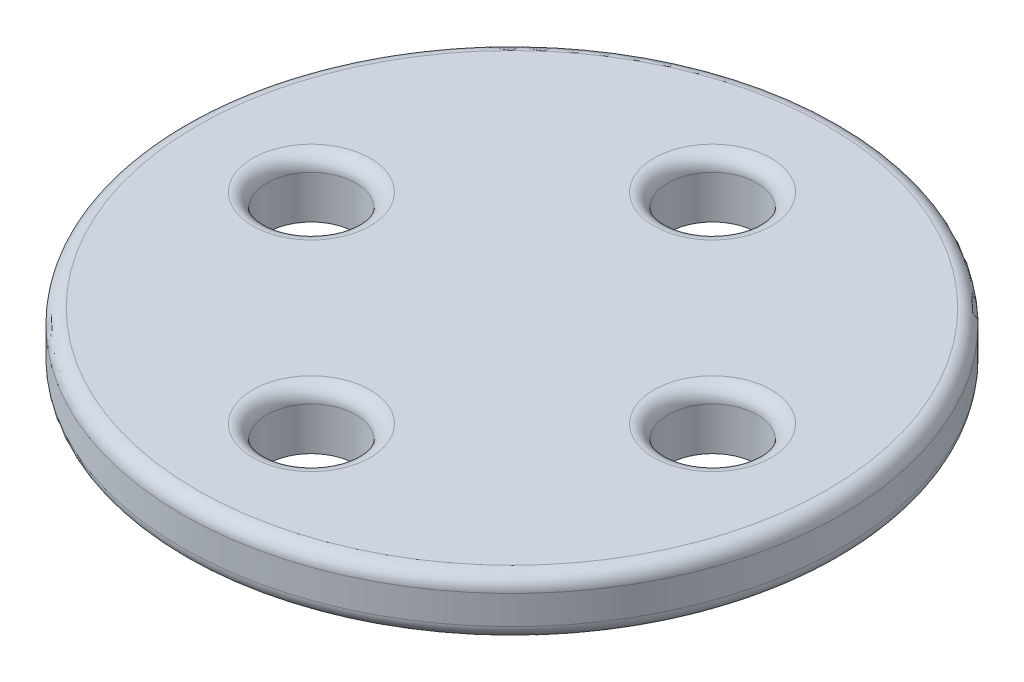
SolidWorks part; units mm, degrees
other "graphite_1"
other "blue_2"
other "white_6"
other "white_7"
other "white_10"
other "white_3"
other "white_2"
ref_plane "Front Plane" through (0, 0, 0) normal (0, 0, 1) x (1, 0, 0)
ref_plane "Top Plane" through (0, 0, 0) normal (0, 1, 0) x (1, 0, 0)
ref_plane "Right Plane" through (0, 0, 0) normal (1, 0, 0) x (0, 0, -1)
sketch "Sketch1" plane through (0, 0, 0) normal (0, 1, 0) x (1, 0, 0)
  line L0 (0, 7) -> (0, 0) construction
  circle A0 centre (0, 0) radius 11.5
  circle A1 centre (0, 7) radius 1.55
  circle A2 centre (7, 0) radius 1.55
  circle A3 centre (0, -7) radius 1.55
  circle A4 centre (-7, 0) radius 1.55
  point P14 (0, 0)
  dimension "D1" = 23
  dimension "D2" = 3.1
  dimension "D3" = 7
  dimension "D4" = 4
extrude "Boss-Extrude1" add sketch "Sketch1" along normal blind 2
fillet "Fillet1" radius 0.5 6 edges at (-7, 2, 1.55) (7, 2, 1.55) (0, 2, 11.5) (0, 2, -5.45) (0, 2, 8.55) (0, 0, 11.5)
sketch "Sketch2" [suppressed] plane through (0, 2, 0) normal (0, 1, 0) x (1, 0, 0)
  line L0 (-2.4749, -2.4749) -> (2.4749, 2.4749) construction
  line L3 (-4.2426, -0.7071) -> (0.7071, 4.2426) construction
  line L4 (-0.7071, -4.2426) -> (4.2426, 0.7071) construction
  line L5 (0, 0) -> (23.072, 0) construction
  line L6 (-6.364, -2.1213) -> (-2.1213, -6.364) construction
  line L7 (-2.1213, -6.364) -> (6.364, 2.1213) construction
  line L8 (6.364, 2.1213) -> (2.1213, 6.364) construction
  line L9 (2.1213, 6.364) -> (-6.364, -2.1213) construction
  line L10 (-6.364, -2.1213) -> (6.364, 2.1213) construction
  line L11 (2.1213, 6.364) -> (6.364, 2.1213)
  line L12 (6.364, 2.1213) -> (4.9497, 0.7071)
  line L13 (2.1213, 6.364) -> (0.7071, 4.9497)
  line L14 (-6.364, -2.1213) -> (-4.9497, -0.7071)
  line L15 (-6.364, -2.1213) -> (-2.1213, -6.364)
  line L16 (-2.1213, -6.364) -> (-0.7071, -4.9497)
  circle A0 centre (-7, 0) radius 2.75 construction
  circle A1 centre (0, 7) radius 2.75 construction
  circle A2 centre (7, 0) radius 2.75 construction
  circle A3 centre (0, -7) radius 2.75 construction
  arc A6 (-4.2426, -0.7071) -> (-0.7071, -4.2426) centre (-2.4749, -2.4749) ccw construction
  arc A7 (4.2426, 0.7071) -> (0.7071, 4.2426) centre (2.4749, 2.4749) ccw construction
  circle A8 centre (0, 0) radius 5 construction
  arc A10 (-0.7071, -4.9497) -> (4.9497, 0.7071) centre (0, 0) ccw
  arc A12 (0.7071, 4.9497) -> (-4.9497, -0.7071) centre (0, 0) ccw
  point P13 (0, 0)
  dimension "D1" = 5.5
  dimension "D2" = 12
  dimension "D3" = 5
  dimension "D7" = 10
  dimension "D4" = 45
  dimension "D5" = 6
  dimension "D6" = 12
extrude "Cable hole" [suppressed] cut sketch "Sketch2" against normal through all
fillet "Fillet2" [suppressed] radius 1
sketch "GL_F_side_blue" plane through (0, 0, 0) normal (0, 1, 0) x (1, 0, 0)
  line L0 (4.1012, -5.7912) -> (3.5426, -5.2326)
  line L1 (3.5426, -5.2326) -> (4.0376, -4.7376)
  line L2 (4.0376, -4.7376) -> (3.7477, -4.4477)
  line L3 (3.7477, -4.4477) -> (3.2527, -4.9427)
  line L4 (3.2527, -4.9427) -> (2.6941, -4.3841)
  line L5 (2.6941, -4.3841) -> (3.1891, -3.8891)
  line L6 (3.1891, -3.8891) -> (1.2092, -1.9092)
  line L7 (1.2092, -1.9092) -> (1.3233, -1.795)
  line L8 (1.3233, -1.795) -> (-1.795, -1.795)
  line L9 (-1.795, -1.795) -> (-1.795, 1.3233)
  line L10 (-1.795, 1.3233) -> (-1.9092, 1.2092)
  line L11 (-1.9092, 1.2092) -> (-4.852, 4.1519)
  line L12 (-4.852, 4.1519) -> (-4.7161, 4.1794)
  line L13 (-4.7161, 4.1794) -> (-4.5701, 4.2398)
  line L14 (-4.5701, 4.2398) -> (-4.3805, 4.3805)
  line L15 (-4.3805, 4.3805) -> (-4.2398, 4.5701)
  line L16 (-4.2398, 4.5701) -> (-4.1794, 4.7161)
  line L17 (-4.1794, 4.7161) -> (-4.1519, 4.852)
  line L18 (-4.1519, 4.852) -> (-1.2092, 1.9092)
  line L19 (-1.2092, 1.9092) -> (-1.3233, 1.795)
  line L20 (-1.3233, 1.795) -> (1.3233, 1.795)
  line L21 (1.3233, 1.795) -> (1.2092, 1.9092)
  line L22 (1.2092, 1.9092) -> (5.6637, 6.3638)
  line L23 (5.6637, 6.3638) -> (5.6872, 6.2571)
  line L24 (5.6872, 6.2571) -> (5.7514, 6.1022)
  line L25 (5.7514, 6.1022) -> (5.9008, 5.9008)
  line L26 (5.9008, 5.9008) -> (6.1022, 5.7514)
  line L27 (6.1022, 5.7514) -> (6.2571, 5.6872)
  line L28 (6.2571, 5.6872) -> (6.3638, 5.6637)
  line L29 (6.3638, 5.6637) -> (1.9092, 1.2092)
  line L30 (1.9092, 1.2092) -> (1.795, 1.3233)
  line L31 (1.795, 1.3233) -> (1.795, -1.3233)
  line L32 (1.795, -1.3233) -> (1.9092, -1.2092)
  line L33 (1.9092, -1.2092) -> (3.8891, -3.1891)
  line L34 (3.8891, -3.1891) -> (4.3841, -2.6941)
  line L35 (4.3841, -2.6941) -> (4.9427, -3.2527)
  line L36 (4.9427, -3.2527) -> (4.4477, -3.7477)
  line L37 (4.4477, -3.7477) -> (4.7376, -4.0376)
  line L38 (4.7376, -4.0376) -> (5.2326, -3.5426)
  line L39 (5.2326, -3.5426) -> (5.7912, -4.1012)
  line L40 (5.7912, -4.1012) -> (5.2962, -4.5962)
  line L41 (5.2962, -4.5962) -> (6.9933, -6.2933)
  line L42 (6.9933, -6.2933) -> (6.2933, -6.9933)
  line L43 (6.2933, -6.9933) -> (4.5962, -5.2962)
  line L44 (4.5962, -5.2962) -> (4.1012, -5.7912)
  line L45 (-0.2962, 0.7941) -> (-0.2962, 0.9029)
  line L46 (-0.2962, 0.9029) -> (-0.3174, 1.0096)
  line L47 (-0.3174, 1.0096) -> (-0.359, 1.1102)
  line L48 (-0.359, 1.1102) -> (-0.4195, 1.2006)
  line L49 (-0.4195, 1.2006) -> (-0.4964, 1.2776)
  line L50 (-0.4964, 1.2776) -> (-0.5869, 1.338)
  line L51 (-0.5869, 1.338) -> (-0.6874, 1.3797)
  line L52 (-0.6874, 1.3797) -> (-0.7941, 1.4009)
  line L53 (-0.7941, 1.4009) -> (-0.9029, 1.4009)
  line L54 (-0.9029, 1.4009) -> (-1.0096, 1.3797)
  line L55 (-1.0096, 1.3797) -> (-1.1102, 1.338)
  line L56 (-1.1102, 1.338) -> (-1.2006, 1.2776)
  line L57 (-1.2006, 1.2776) -> (-1.2776, 1.2006)
  line L58 (-1.2776, 1.2006) -> (-1.338, 1.1102)
  line L59 (-1.338, 1.1102) -> (-1.3797, 1.0096)
  line L60 (-1.3797, 1.0096) -> (-1.4009, 0.9029)
  line L61 (-1.4009, 0.9029) -> (-1.4009, 0.7941)
  line L62 (-1.4009, 0.7941) -> (-1.3797, 0.6874)
  line L63 (-1.3797, 0.6874) -> (-1.338, 0.5869)
  line L64 (-1.338, 0.5869) -> (-1.2776, 0.4964)
  line L65 (-1.2776, 0.4964) -> (-1.2006, 0.4195)
  line L66 (-1.2006, 0.4195) -> (-1.1102, 0.359)
  line L67 (-1.1102, 0.359) -> (-1.0096, 0.3174)
  line L68 (-1.0096, 0.3174) -> (-0.9029, 0.2962)
  line L69 (-0.9029, 0.2962) -> (-0.7941, 0.2962)
  line L70 (-0.7941, 0.2962) -> (-0.6874, 0.3174)
  line L71 (-0.6874, 0.3174) -> (-0.5869, 0.359)
  line L72 (-0.5869, 0.359) -> (-0.4964, 0.4195)
  line L73 (-0.4964, 0.4195) -> (-0.4195, 0.4964)
  line L74 (-0.4195, 0.4964) -> (-0.359, 0.5869)
  line L75 (-0.359, 0.5869) -> (-0.3174, 0.6874)
  line L76 (-0.3174, 0.6874) -> (-0.2962, 0.7941)
extrude "GL_F_side_blue_raised" add sketch "GL_F_side_blue" along normal blind 0.6 from offset 0.6 separate body offset against normal yes
sketch "GL_F_side_white" plane through (0, 0, 0) normal (0, 1, 0) x (1, 0, 0)
  line L0 (-5.628, -6.3839) -> (-5.6958, -6.4665)
  line L1 (-5.6958, -6.4665) -> (-5.7783, -6.5342)
  line L2 (-5.7783, -6.5342) -> (-5.8726, -6.5846)
  line L3 (-5.8726, -6.5846) -> (-5.9748, -6.6156)
  line L4 (-5.9748, -6.6156) -> (-6.0811, -6.6261)
  line L5 (-6.0811, -6.6261) -> (-6.1874, -6.6156)
  line L6 (-6.1874, -6.6156) -> (-6.2897, -6.5846)
  line L7 (-6.2897, -6.5846) -> (-6.3839, -6.5342)
  line L8 (-6.3839, -6.5342) -> (-6.4665, -6.4665)
  line L9 (-6.4665, -6.4665) -> (-6.5342, -6.3839)
  line L10 (-6.5342, -6.3839) -> (-6.5846, -6.2897)
  line L11 (-6.5846, -6.2897) -> (-6.6156, -6.1874)
  line L12 (-6.6156, -6.1874) -> (-6.6261, -6.0811)
  line L13 (-6.6261, -6.0811) -> (-6.6156, -5.9748)
  line L14 (-6.6156, -5.9748) -> (-6.5846, -5.8726)
  line L15 (-6.5846, -5.8726) -> (-6.5342, -5.7783)
  line L16 (-6.5342, -5.7783) -> (-6.4665, -5.6958)
  line L17 (-6.4665, -5.6958) -> (-6.3839, -5.628)
  line L18 (-6.3839, -5.628) -> (-6.2897, -5.5776)
  line L19 (-6.2897, -5.5776) -> (-6.1874, -5.5466)
  line L20 (-6.1874, -5.5466) -> (-6.0811, -5.5361)
  line L21 (-6.0811, -5.5361) -> (-5.9748, -5.5466)
  line L22 (-5.9748, -5.5466) -> (-5.8726, -5.5776)
  line L23 (-5.8726, -5.5776) -> (-5.7783, -5.628)
  line L24 (-5.7783, -5.628) -> (-5.6958, -5.6958)
  line L25 (-5.6958, -5.6958) -> (-5.628, -5.7783)
  line L26 (-5.628, -5.7783) -> (-5.5776, -5.8726)
  line L27 (-5.5776, -5.8726) -> (-5.5466, -5.9748)
  line L28 (-5.5466, -5.9748) -> (-5.5361, -6.0811)
  line L29 (-5.5361, -6.0811) -> (-5.5466, -6.1874)
  line L30 (-5.5466, -6.1874) -> (-5.5776, -6.2897)
  line L31 (-5.5776, -6.2897) -> (-5.628, -6.3839)
  line L32 (-3.7895, -4.5454) -> (-3.8573, -4.628)
  line L33 (-3.8573, -4.628) -> (-3.9399, -4.6958)
  line L34 (-3.9399, -4.6958) -> (-4.0341, -4.7461)
  line L35 (-4.0341, -4.7461) -> (-4.1363, -4.7771)
  line L36 (-4.1363, -4.7771) -> (-4.2426, -4.7876)
  line L37 (-4.2426, -4.7876) -> (-4.349, -4.7771)
  line L38 (-4.349, -4.7771) -> (-4.4512, -4.7461)
  line L39 (-4.4512, -4.7461) -> (-4.5454, -4.6958)
  line L40 (-4.5454, -4.6958) -> (-4.628, -4.628)
  line L41 (-4.628, -4.628) -> (-4.6958, -4.5454)
  line L42 (-4.6958, -4.5454) -> (-4.7461, -4.4512)
  line L43 (-4.7461, -4.4512) -> (-4.7771, -4.349)
  line L44 (-4.7771, -4.349) -> (-4.7876, -4.2426)
  line L45 (-4.7876, -4.2426) -> (-4.7771, -4.1363)
  line L46 (-4.7771, -4.1363) -> (-4.7461, -4.0341)
  line L47 (-4.7461, -4.0341) -> (-4.6958, -3.9399)
  line L48 (-4.6958, -3.9399) -> (-4.628, -3.8573)
  line L49 (-4.628, -3.8573) -> (-4.5454, -3.7895)
  line L50 (-4.5454, -3.7895) -> (-4.4512, -3.7391)
  line L51 (-4.4512, -3.7391) -> (-4.349, -3.7081)
  line L52 (-4.349, -3.7081) -> (-4.2426, -3.6977)
  line L53 (-4.2426, -3.6977) -> (-4.1363, -3.7081)
  line L54 (-4.1363, -3.7081) -> (-4.0341, -3.7391)
  line L55 (-4.0341, -3.7391) -> (-3.9399, -3.7895)
  line L56 (-3.9399, -3.7895) -> (-3.8573, -3.8573)
  line L57 (-3.8573, -3.8573) -> (-3.7895, -3.9399)
  line L58 (-3.7895, -3.9399) -> (-3.7391, -4.0341)
  line L59 (-3.7391, -4.0341) -> (-3.7081, -4.1363)
  line L60 (-3.7081, -4.1363) -> (-3.6977, -4.2426)
  line L61 (-3.6977, -4.2426) -> (-3.7081, -4.349)
  line L62 (-3.7081, -4.349) -> (-3.7391, -4.4512)
  line L63 (-3.7391, -4.4512) -> (-3.7895, -4.5454)
  line L64 (-0.3954, 0.5458) -> (-0.4632, 0.4632)
  line L65 (-0.4632, 0.4632) -> (-0.5458, 0.3954)
  line L66 (-0.5458, 0.3954) -> (-0.64, 0.345)
  line L67 (-0.64, 0.345) -> (-0.7422, 0.314)
  line L68 (-0.7422, 0.314) -> (-0.8485, 0.3036)
  line L69 (-0.8485, 0.3036) -> (-0.9548, 0.314)
  line L70 (-0.9548, 0.314) -> (-1.0571, 0.345)
  line L71 (-1.0571, 0.345) -> (-1.1513, 0.3954)
  line L72 (-1.1513, 0.3954) -> (-1.2339, 0.4632)
  line L73 (-1.2339, 0.4632) -> (-1.3017, 0.5458)
  line L74 (-1.3017, 0.5458) -> (-1.352, 0.64)
  line L75 (-1.352, 0.64) -> (-1.383, 0.7422)
  line L76 (-1.383, 0.7422) -> (-1.3935, 0.8485)
  line L77 (-1.3935, 0.8485) -> (-1.383, 0.9548)
  line L78 (-1.383, 0.9548) -> (-1.352, 1.0571)
  line L79 (-1.352, 1.0571) -> (-1.3017, 1.1513)
  line L80 (-1.3017, 1.1513) -> (-1.2339, 1.2339)
  line L81 (-1.2339, 1.2339) -> (-1.1513, 1.3017)
  line L82 (-1.1513, 1.3017) -> (-1.0571, 1.352)
  line L83 (-1.0571, 1.352) -> (-0.9548, 1.383)
  line L84 (-0.9548, 1.383) -> (-0.8485, 1.3935)
  line L85 (-0.8485, 1.3935) -> (-0.7422, 1.383)
  line L86 (-0.7422, 1.383) -> (-0.64, 1.352)
  line L87 (-0.64, 1.352) -> (-0.5458, 1.3017)
  line L88 (-0.5458, 1.3017) -> (-0.4632, 1.2339)
  line L89 (-0.4632, 1.2339) -> (-0.3954, 1.1513)
  line L90 (-0.3954, 1.1513) -> (-0.345, 1.0571)
  line L91 (-0.345, 1.0571) -> (-0.314, 0.9548)
  line L92 (-0.314, 0.9548) -> (-0.3036, 0.8485)
  line L93 (-0.3036, 0.8485) -> (-0.314, 0.7422)
  line L94 (-0.314, 0.7422) -> (-0.345, 0.64)
  line L95 (-0.345, 0.64) -> (-0.3954, 0.5458)
  line L96 (-4.3876, 4.3876) -> (-4.5081, 4.2887)
  line L97 (-4.5081, 4.2887) -> (-4.6455, 4.2153)
  line L98 (-4.6455, 4.2153) -> (-4.7947, 4.17)
  line L99 (-4.7947, 4.17) -> (-4.9497, 4.1548)
  line L100 (-4.9497, 4.1548) -> (-5.1048, 4.17)
  line L101 (-5.1048, 4.17) -> (-5.254, 4.2153)
  line L102 (-5.254, 4.2153) -> (-5.3914, 4.2887)
  line L103 (-5.3914, 4.2887) -> (-5.5119, 4.3876)
  line L104 (-5.5119, 4.3876) -> (-5.6107, 4.5081)
  line L105 (-5.6107, 4.5081) -> (-5.6842, 4.6455)
  line L106 (-5.6842, 4.6455) -> (-5.7294, 4.7947)
  line L107 (-5.7294, 4.7947) -> (-5.7447, 4.9497)
  line L108 (-5.7447, 4.9497) -> (-5.7294, 5.1048)
  line L109 (-5.7294, 5.1048) -> (-5.6842, 5.254)
  line L110 (-5.6842, 5.254) -> (-5.6107, 5.3914)
  line L111 (-5.6107, 5.3914) -> (-5.5119, 5.5119)
  line L112 (-5.5119, 5.5119) -> (-5.3914, 5.6107)
  line L113 (-5.3914, 5.6107) -> (-5.254, 5.6842)
  line L114 (-5.254, 5.6842) -> (-5.1048, 5.7294)
  line L115 (-5.1048, 5.7294) -> (-4.9497, 5.7447)
  line L116 (-4.9497, 5.7447) -> (-4.7947, 5.7294)
  line L117 (-4.7947, 5.7294) -> (-4.6455, 5.6842)
  line L118 (-4.6455, 5.6842) -> (-4.5081, 5.6107)
  line L119 (-4.5081, 5.6107) -> (-4.3876, 5.5119)
  line L120 (-4.3876, 5.5119) -> (-4.2887, 5.3914)
  line L121 (-4.2887, 5.3914) -> (-4.2153, 5.254)
  line L122 (-4.2153, 5.254) -> (-4.17, 5.1048)
  line L123 (-4.17, 5.1048) -> (-4.1548, 4.9497)
  line L124 (-4.1548, 4.9497) -> (-4.17, 4.7947)
  line L125 (-4.17, 4.7947) -> (-4.2153, 4.6455)
  line L126 (-4.2153, 4.6455) -> (-4.2887, 4.5081)
  line L127 (-4.2887, 4.5081) -> (-4.3876, 4.3876)
  line L128 (7.1029, 5.9079) -> (6.9748, 5.8028)
  line L129 (6.9748, 5.8028) -> (6.8287, 5.7247)
  line L130 (6.8287, 5.7247) -> (6.6702, 5.6766)
  line L131 (6.6702, 5.6766) -> (6.5054, 5.6604)
  line L132 (6.5054, 5.6604) -> (6.3405, 5.6766)
  line L133 (6.3405, 5.6766) -> (6.182, 5.7247)
  line L134 (6.182, 5.7247) -> (6.0359, 5.8028)
  line L135 (6.0359, 5.8028) -> (5.9079, 5.9079)
  line L136 (5.9079, 5.9079) -> (5.8028, 6.0359)
  line L137 (5.8028, 6.0359) -> (5.7247, 6.182)
  line L138 (5.7247, 6.182) -> (5.6766, 6.3405)
  line L139 (5.6766, 6.3405) -> (5.6604, 6.5054)
  line L140 (5.6604, 6.5054) -> (5.6766, 6.6702)
  line L141 (5.6766, 6.6702) -> (5.7247, 6.8287)
  line L142 (5.7247, 6.8287) -> (5.8028, 6.9748)
  line L143 (5.8028, 6.9748) -> (5.9079, 7.1029)
  line L144 (5.9079, 7.1029) -> (6.0359, 7.208)
  line L145 (6.0359, 7.208) -> (6.182, 7.286)
  line L146 (6.182, 7.286) -> (6.3405, 7.3341)
  line L147 (6.3405, 7.3341) -> (6.5054, 7.3504)
  line L148 (6.5054, 7.3504) -> (6.6702, 7.3341)
  line L149 (6.6702, 7.3341) -> (6.8287, 7.286)
  line L150 (6.8287, 7.286) -> (6.9748, 7.208)
  line L151 (6.9748, 7.208) -> (7.1029, 7.1029)
  line L152 (7.1029, 7.1029) -> (7.208, 6.9748)
  line L153 (7.208, 6.9748) -> (7.286, 6.8287)
  line L154 (7.286, 6.8287) -> (7.3341, 6.6702)
  line L155 (7.3341, 6.6702) -> (7.3504, 6.5054)
  line L156 (7.3504, 6.5054) -> (7.3341, 6.3405)
  line L157 (7.3341, 6.3405) -> (7.286, 6.182)
  line L158 (7.286, 6.182) -> (7.208, 6.0359)
  line L159 (7.208, 6.0359) -> (7.1029, 5.9079)
extrude "GL_F_side_white_raised" add sketch "GL_F_side_white" along normal blind 0.6 from offset 0.6 separate body offset against normal yes
sketch "GL_E_side_blue" plane through (0, 0, 0) normal (0, 1, 0) x (1, 0, 0)
  line L0 (4.3841, -6.074) -> (3.8254, -5.5154)
  line L1 (3.8254, -5.5154) -> (4.3204, -5.0205)
  line L2 (4.3204, -5.0205) -> (4.0305, -4.7305)
  line L3 (4.0305, -4.7305) -> (3.5355, -5.2255)
  line L4 (3.5355, -5.2255) -> (2.9769, -4.6669)
  line L5 (2.9769, -4.6669) -> (3.4719, -4.1719)
  line L6 (3.4719, -4.1719) -> (3.182, -3.882)
  line L7 (3.182, -3.882) -> (2.687, -4.377)
  line L8 (2.687, -4.377) -> (2.1284, -3.8184)
  line L9 (2.1284, -3.8184) -> (2.6234, -3.3234)
  line L10 (2.6234, -3.3234) -> (0.8839, -1.5839)
  line L11 (0.8839, -1.5839) -> (0, -2.4678)
  line L12 (0, -2.4678) -> (-0.8839, -1.5839)
  line L13 (-0.8839, -1.5839) -> (-3.4994, -4.1994)
  line L14 (-3.4994, -4.1994) -> (-3.7618, -5.6882)
  line L15 (-3.7618, -5.6882) -> (-3.8485, -5.6032)
  line L16 (-3.8485, -5.6032) -> (-3.9798, -5.5155)
  line L17 (-3.9798, -5.5155) -> (-4.202, -5.436)
  line L18 (-4.202, -5.436) -> (-4.3592, -5.4205)
  line L19 (-4.3592, -5.4205) -> (-4.5164, -5.436)
  line L20 (-4.5164, -5.436) -> (-4.7368, -5.5165)
  line L21 (-4.7368, -5.5165) -> (-4.4202, -3.7202)
  line L22 (-4.4202, -3.7202) -> (-1.5839, -0.8839)
  line L23 (-1.5839, -0.8839) -> (-2.4678, 0)
  line L24 (-2.4678, 0) -> (0, 2.4678)
  line L25 (0, 2.4678) -> (0.8839, 1.5839)
  line L26 (0.8839, 1.5839) -> (5.5223, 6.2223)
  line L27 (5.5223, 6.2223) -> (5.5458, 6.1157)
  line L28 (5.5458, 6.1157) -> (5.6099, 5.9608)
  line L29 (5.6099, 5.9608) -> (5.7593, 5.7593)
  line L30 (5.7593, 5.7593) -> (5.9608, 5.6099)
  line L31 (5.9608, 5.6099) -> (6.1157, 5.5458)
  line L32 (6.1157, 5.5458) -> (6.2223, 5.5223)
  line L33 (6.2223, 5.5223) -> (1.5839, 0.8839)
  line L34 (1.5839, 0.8839) -> (2.4678, 0)
  line L35 (2.4678, 0) -> (1.5839, -0.8839)
  line L36 (1.5839, -0.8839) -> (3.3234, -2.6234)
  line L37 (3.3234, -2.6234) -> (3.8184, -2.1284)
  line L38 (3.8184, -2.1284) -> (4.377, -2.687)
  line L39 (4.377, -2.687) -> (3.882, -3.182)
  line L40 (3.882, -3.182) -> (4.1719, -3.4719)
  line L41 (4.1719, -3.4719) -> (4.6669, -2.9769)
  line L42 (4.6669, -2.9769) -> (5.2255, -3.5355)
  line L43 (5.2255, -3.5355) -> (4.7305, -4.0305)
  line L44 (4.7305, -4.0305) -> (5.0205, -4.3204)
  line L45 (5.0205, -4.3204) -> (5.5154, -3.8254)
  line L46 (5.5154, -3.8254) -> (6.074, -4.3841)
  line L47 (6.074, -4.3841) -> (5.5791, -4.879)
  line L48 (5.5791, -4.879) -> (7.1347, -6.4347)
  line L49 (7.1347, -6.4347) -> (6.4347, -7.1347)
  line L50 (6.4347, -7.1347) -> (4.879, -5.5791)
  line L51 (4.879, -5.5791) -> (4.3841, -6.074)
  line L52 (0.5524, 0.9456) -> (0.5524, 1.0544)
  line L53 (0.5524, 1.0544) -> (0.5311, 1.1611)
  line L54 (0.5311, 1.1611) -> (0.4895, 1.2616)
  line L55 (0.4895, 1.2616) -> (0.429, 1.3521)
  line L56 (0.429, 1.3521) -> (0.3521, 1.429)
  line L57 (0.3521, 1.429) -> (0.2616, 1.4895)
  line L58 (0.2616, 1.4895) -> (0.1611, 1.5311)
  line L59 (0.1611, 1.5311) -> (0.0544, 1.5524)
  line L60 (0.0544, 1.5524) -> (-0.0544, 1.5524)
  line L61 (-0.0544, 1.5524) -> (-0.1611, 1.5311)
  line L62 (-0.1611, 1.5311) -> (-0.2616, 1.4895)
  line L63 (-0.2616, 1.4895) -> (-0.3521, 1.429)
  line L64 (-0.3521, 1.429) -> (-0.429, 1.3521)
  line L65 (-0.429, 1.3521) -> (-0.4895, 1.2616)
  line L66 (-0.4895, 1.2616) -> (-0.5311, 1.1611)
  line L67 (-0.5311, 1.1611) -> (-0.5524, 1.0544)
  line L68 (-0.5524, 1.0544) -> (-0.5524, 0.9456)
  line L69 (-0.5524, 0.9456) -> (-0.5311, 0.8389)
  line L70 (-0.5311, 0.8389) -> (-0.4895, 0.7384)
  line L71 (-0.4895, 0.7384) -> (-0.429, 0.6479)
  line L72 (-0.429, 0.6479) -> (-0.3521, 0.571)
  line L73 (-0.3521, 0.571) -> (-0.2616, 0.5105)
  line L74 (-0.2616, 0.5105) -> (-0.1611, 0.4689)
  line L75 (-0.1611, 0.4689) -> (-0.0544, 0.4476)
  line L76 (-0.0544, 0.4476) -> (0.0544, 0.4476)
  line L77 (0.0544, 0.4476) -> (0.1611, 0.4689)
  line L78 (0.1611, 0.4689) -> (0.2616, 0.5105)
  line L79 (0.2616, 0.5105) -> (0.3521, 0.571)
  line L80 (0.3521, 0.571) -> (0.429, 0.6479)
  line L81 (0.429, 0.6479) -> (0.4895, 0.7384)
  line L82 (0.4895, 0.7384) -> (0.5311, 0.8389)
  line L83 (0.5311, 0.8389) -> (0.5524, 0.9456)
extrude "GL_E_side_blue_raised" [suppressed] add sketch "GL_E_side_blue" along normal blind 0.6 from offset 2 separate body
sketch "GL_E_side_white" plane through (0, 0, 0) normal (0, 1, 0) x (1, 0, 0)
  line L0 (-3.6982, -6.6672) -> (-3.797, -6.7877)
  line L1 (-3.797, -6.7877) -> (-3.9175, -6.8866)
  line L2 (-3.9175, -6.8866) -> (-4.055, -6.96)
  line L3 (-4.055, -6.96) -> (-4.2041, -7.0053)
  line L4 (-4.2041, -7.0053) -> (-4.3592, -7.0205)
  line L5 (-4.3592, -7.0205) -> (-4.5143, -7.0053)
  line L6 (-4.5143, -7.0053) -> (-4.6634, -6.96)
  line L7 (-4.6634, -6.96) -> (-4.8008, -6.8866)
  line L8 (-4.8008, -6.8866) -> (-4.9213, -6.7877)
  line L9 (-4.9213, -6.7877) -> (-5.0202, -6.6672)
  line L10 (-5.0202, -6.6672) -> (-5.0936, -6.5298)
  line L11 (-5.0936, -6.5298) -> (-5.1389, -6.3806)
  line L12 (-5.1389, -6.3806) -> (-5.1542, -6.2256)
  line L13 (-5.1542, -6.2256) -> (-5.1389, -6.0705)
  line L14 (-5.1389, -6.0705) -> (-5.0936, -5.9213)
  line L15 (-5.0936, -5.9213) -> (-5.0202, -5.7839)
  line L16 (-5.0202, -5.7839) -> (-4.9213, -5.6634)
  line L17 (-4.9213, -5.6634) -> (-4.8008, -5.5646)
  line L18 (-4.8008, -5.5646) -> (-4.6634, -5.4911)
  line L19 (-4.6634, -5.4911) -> (-4.5143, -5.4459)
  line L20 (-4.5143, -5.4459) -> (-4.3592, -5.4306)
  line L21 (-4.3592, -5.4306) -> (-4.2041, -5.4459)
  line L22 (-4.2041, -5.4459) -> (-4.055, -5.4911)
  line L23 (-4.055, -5.4911) -> (-3.9175, -5.5646)
  line L24 (-3.9175, -5.5646) -> (-3.797, -5.6634)
  line L25 (-3.797, -5.6634) -> (-3.6982, -5.7839)
  line L26 (-3.6982, -5.7839) -> (-3.6247, -5.9213)
  line L27 (-3.6247, -5.9213) -> (-3.5795, -6.0705)
  line L28 (-3.5795, -6.0705) -> (-3.5642, -6.2256)
  line L29 (-3.5642, -6.2256) -> (-3.5795, -6.3806)
  line L30 (-3.5795, -6.3806) -> (-3.6247, -6.5298)
  line L31 (-3.6247, -6.5298) -> (-3.6982, -6.6672)
  line L32 (0.4531, 0.6972) -> (0.3854, 0.6146)
  line L33 (0.3854, 0.6146) -> (0.3028, 0.5469)
  line L34 (0.3028, 0.5469) -> (0.2086, 0.4965)
  line L35 (0.2086, 0.4965) -> (0.1063, 0.4655)
  line L36 (0.1063, 0.4655) -> (0, 0.455)
  line L37 (0, 0.455) -> (-0.1063, 0.4655)
  line L38 (-0.1063, 0.4655) -> (-0.2086, 0.4965)
  line L39 (-0.2086, 0.4965) -> (-0.3028, 0.5469)
  line L40 (-0.3028, 0.5469) -> (-0.3854, 0.6146)
  line L41 (-0.3854, 0.6146) -> (-0.4531, 0.6972)
  line L42 (-0.4531, 0.6972) -> (-0.5035, 0.7914)
  line L43 (-0.5035, 0.7914) -> (-0.5345, 0.8937)
  line L44 (-0.5345, 0.8937) -> (-0.545, 1)
  line L45 (-0.545, 1) -> (-0.5345, 1.1063)
  line L46 (-0.5345, 1.1063) -> (-0.5035, 1.2086)
  line L47 (-0.5035, 1.2086) -> (-0.4531, 1.3028)
  line L48 (-0.4531, 1.3028) -> (-0.3854, 1.3854)
  line L49 (-0.3854, 1.3854) -> (-0.3028, 1.4531)
  line L50 (-0.3028, 1.4531) -> (-0.2086, 1.5035)
  line L51 (-0.2086, 1.5035) -> (-0.1063, 1.5345)
  line L52 (-0.1063, 1.5345) -> (0, 1.545)
  line L53 (0, 1.545) -> (0.1063, 1.5345)
  line L54 (0.1063, 1.5345) -> (0.2086, 1.5035)
  line L55 (0.2086, 1.5035) -> (0.3028, 1.4531)
  line L56 (0.3028, 1.4531) -> (0.3854, 1.3854)
  line L57 (0.3854, 1.3854) -> (0.4531, 1.3028)
  line L58 (0.4531, 1.3028) -> (0.5035, 1.2086)
  line L59 (0.5035, 1.2086) -> (0.5345, 1.1063)
  line L60 (0.5345, 1.1063) -> (0.545, 1)
  line L61 (0.545, 1) -> (0.5345, 0.8937)
  line L62 (0.5345, 0.8937) -> (0.5035, 0.7914)
  line L63 (0.5035, 0.7914) -> (0.4531, 0.6972)
  line L64 (-3.9309, 4.0813) -> (-3.9987, 3.9987)
  line L65 (-3.9987, 3.9987) -> (-4.0813, 3.9309)
  line L66 (-4.0813, 3.9309) -> (-4.1755, 3.8806)
  line L67 (-4.1755, 3.8806) -> (-4.2777, 3.8496)
  line L68 (-4.2777, 3.8496) -> (-4.3841, 3.8391)
  line L69 (-4.3841, 3.8391) -> (-4.4904, 3.8496)
  line L70 (-4.4904, 3.8496) -> (-4.5926, 3.8806)
  line L71 (-4.5926, 3.8806) -> (-4.6868, 3.9309)
  line L72 (-4.6868, 3.9309) -> (-4.7694, 3.9987)
  line L73 (-4.7694, 3.9987) -> (-4.8372, 4.0813)
  line L74 (-4.8372, 4.0813) -> (-4.8876, 4.1755)
  line L75 (-4.8876, 4.1755) -> (-4.9186, 4.2777)
  line L76 (-4.9186, 4.2777) -> (-4.929, 4.3841)
  line L77 (-4.929, 4.3841) -> (-4.9186, 4.4904)
  line L78 (-4.9186, 4.4904) -> (-4.8876, 4.5926)
  line L79 (-4.8876, 4.5926) -> (-4.8372, 4.6868)
  line L80 (-4.8372, 4.6868) -> (-4.7694, 4.7694)
  line L81 (-4.7694, 4.7694) -> (-4.6868, 4.8372)
  line L82 (-4.6868, 4.8372) -> (-4.5926, 4.8876)
  line L83 (-4.5926, 4.8876) -> (-4.4904, 4.9186)
  line L84 (-4.4904, 4.9186) -> (-4.3841, 4.929)
  line L85 (-4.3841, 4.929) -> (-4.2777, 4.9186)
  line L86 (-4.2777, 4.9186) -> (-4.1755, 4.8876)
  line L87 (-4.1755, 4.8876) -> (-4.0813, 4.8372)
  line L88 (-4.0813, 4.8372) -> (-3.9987, 4.7694)
  line L89 (-3.9987, 4.7694) -> (-3.9309, 4.6868)
  line L90 (-3.9309, 4.6868) -> (-3.8806, 4.5926)
  line L91 (-3.8806, 4.5926) -> (-3.8496, 4.4904)
  line L92 (-3.8496, 4.4904) -> (-3.8391, 4.3841)
  line L93 (-3.8391, 4.3841) -> (-3.8496, 4.2777)
  line L94 (-3.8496, 4.2777) -> (-3.8806, 4.1755)
  line L95 (-3.8806, 4.1755) -> (-3.9309, 4.0813)
  line L96 (-5.519, 5.519) -> (-5.6091, 5.445)
  line L97 (-5.6091, 5.445) -> (-5.712, 5.39)
  line L98 (-5.712, 5.39) -> (-5.8236, 5.3562)
  line L99 (-5.8236, 5.3562) -> (-5.9397, 5.3447)
  line L100 (-5.9397, 5.3447) -> (-6.0558, 5.3562)
  line L101 (-6.0558, 5.3562) -> (-6.1674, 5.39)
  line L102 (-6.1674, 5.39) -> (-6.2702, 5.445)
  line L103 (-6.2702, 5.445) -> (-6.3604, 5.519)
  line L104 (-6.3604, 5.519) -> (-6.4344, 5.6091)
  line L105 (-6.4344, 5.6091) -> (-6.4894, 5.712)
  line L106 (-6.4894, 5.712) -> (-6.5232, 5.8236)
  line L107 (-6.5232, 5.8236) -> (-6.5347, 5.9397)
  line L108 (-6.5347, 5.9397) -> (-6.5232, 6.0558)
  line L109 (-6.5232, 6.0558) -> (-6.4894, 6.1674)
  line L110 (-6.4894, 6.1674) -> (-6.4344, 6.2702)
  line L111 (-6.4344, 6.2702) -> (-6.3604, 6.3604)
  line L112 (-6.3604, 6.3604) -> (-6.2702, 6.4344)
  line L113 (-6.2702, 6.4344) -> (-6.1674, 6.4894)
  line L114 (-6.1674, 6.4894) -> (-6.0558, 6.5232)
  line L115 (-6.0558, 6.5232) -> (-5.9397, 6.5347)
  line L116 (-5.9397, 6.5347) -> (-5.8236, 6.5232)
  line L117 (-5.8236, 6.5232) -> (-5.712, 6.4894)
  line L118 (-5.712, 6.4894) -> (-5.6091, 6.4344)
  line L119 (-5.6091, 6.4344) -> (-5.519, 6.3604)
  line L120 (-5.519, 6.3604) -> (-5.445, 6.2702)
  line L121 (-5.445, 6.2702) -> (-5.39, 6.1674)
  line L122 (-5.39, 6.1674) -> (-5.3562, 6.0558)
  line L123 (-5.3562, 6.0558) -> (-5.3447, 5.9397)
  line L124 (-5.3447, 5.9397) -> (-5.3562, 5.8236)
  line L125 (-5.3562, 5.8236) -> (-5.39, 5.712)
  line L126 (-5.39, 5.712) -> (-5.445, 5.6091)
  line L127 (-5.445, 5.6091) -> (-5.519, 5.519)
  line L128 (6.9614, 5.7665) -> (6.8334, 5.6614)
  line L129 (6.8334, 5.6614) -> (6.6873, 5.5833)
  line L130 (6.6873, 5.5833) -> (6.5288, 5.5352)
  line L131 (6.5288, 5.5352) -> (6.364, 5.519)
  line L132 (6.364, 5.519) -> (6.1991, 5.5352)
  line L133 (6.1991, 5.5352) -> (6.0406, 5.5833)
  line L134 (6.0406, 5.5833) -> (5.8945, 5.6614)
  line L135 (5.8945, 5.6614) -> (5.7665, 5.7665)
  line L136 (5.7665, 5.7665) -> (5.6614, 5.8945)
  line L137 (5.6614, 5.8945) -> (5.5833, 6.0406)
  line L138 (5.5833, 6.0406) -> (5.5352, 6.1991)
  line L139 (5.5352, 6.1991) -> (5.519, 6.364)
  line L140 (5.519, 6.364) -> (5.5352, 6.5288)
  line L141 (5.5352, 6.5288) -> (5.5833, 6.6873)
  line L142 (5.5833, 6.6873) -> (5.6614, 6.8334)
  line L143 (5.6614, 6.8334) -> (5.7665, 6.9614)
  line L144 (5.7665, 6.9614) -> (5.8945, 7.0665)
  line L145 (5.8945, 7.0665) -> (6.0406, 7.1446)
  line L146 (6.0406, 7.1446) -> (6.1991, 7.1927)
  line L147 (6.1991, 7.1927) -> (6.364, 7.2089)
  line L148 (6.364, 7.2089) -> (6.5288, 7.1927)
  line L149 (6.5288, 7.1927) -> (6.6873, 7.1446)
  line L150 (6.6873, 7.1446) -> (6.8334, 7.0665)
  line L151 (6.8334, 7.0665) -> (6.9614, 6.9614)
  line L152 (6.9614, 6.9614) -> (7.0665, 6.8334)
  line L153 (7.0665, 6.8334) -> (7.1446, 6.6873)
  line L154 (7.1446, 6.6873) -> (7.1927, 6.5288)
  line L155 (7.1927, 6.5288) -> (7.2089, 6.364)
  line L156 (7.2089, 6.364) -> (7.1927, 6.1991)
  line L157 (7.1927, 6.1991) -> (7.1446, 6.0406)
  line L158 (7.1446, 6.0406) -> (7.0665, 5.8945)
  line L159 (7.0665, 5.8945) -> (6.9614, 5.7665)
extrude "GL_E_side_white_raised" [suppressed] add sketch "GL_E_side_white" along normal blind 0.6 from offset 2 separate body
